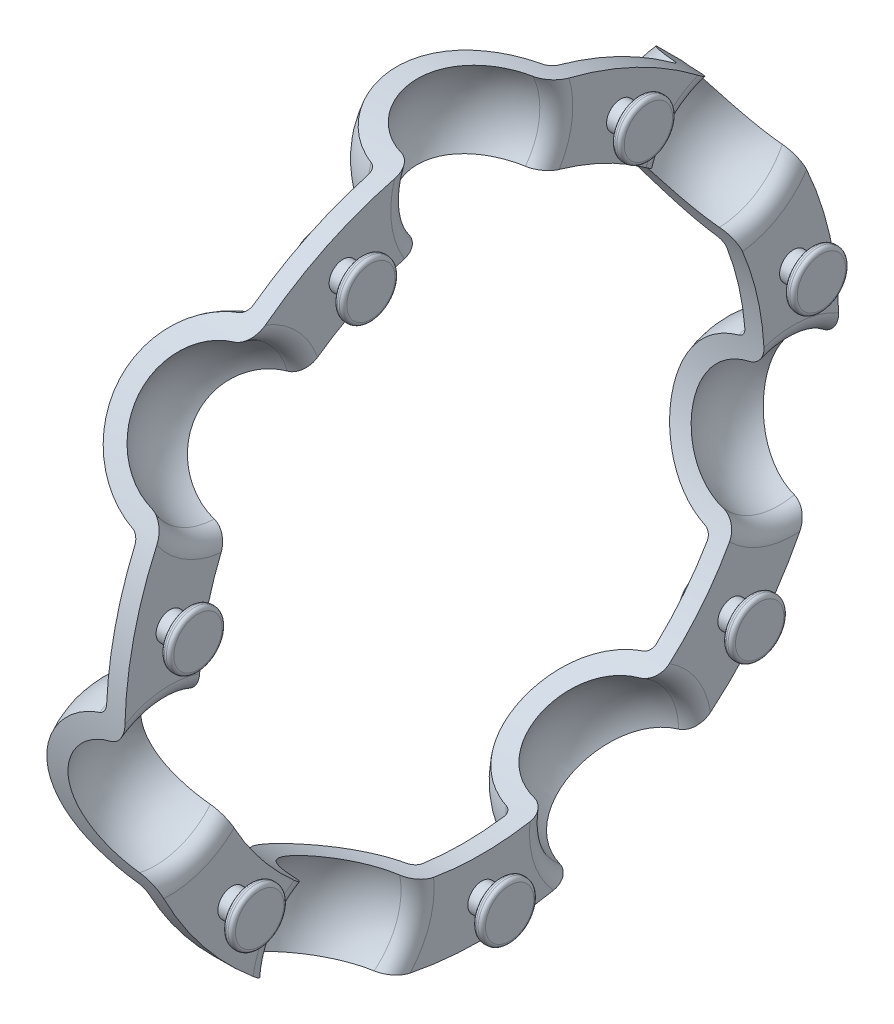
SolidWorks part; units mm, degrees
ref_plane "Front Plane" through (0, 0, 0) normal (0, 0, 1) x (1, 0, 0)
ref_plane "Top Plane" through (0, 0, 0) normal (0, 1, 0) x (1, 0, 0)
ref_plane "Right Plane" through (0, 0, 0) normal (1, 0, 0) x (0, 0, -1)
sketch "Sketch1" plane through (0, 0, 0) normal (1, 0, 0) x (0, 0, -1)
  circle A0 centre (0, 0) radius 23
  dimension "D1" = 46
extrude "Boss-Extrude1" add sketch "Sketch1" along normal blind 1
sketch "Sketch2" plane through (1, 0, 0) normal (1, 0, 0) x (0, 0, -1)
  line L0 (0, 0) -> (0, 17.2) construction
  line L1 (-5, 17.2) -> (5, 17.2)
  arc A0 (-5, 17.2) -> (5, 17.2) centre (0, 17.2) ccw
  point P5 (0, 17.2)
  dimension "D1" = 5
  dimension "D2" = 17.2
revolve "Revolve1" add sketch "Sketch2" angle 180 about L1
sketch "Sketch3" plane through (1, 0, 0) normal (1, 0, 0) x (0, 0, -1)
  line L0 (-4, 17.2) -> (4, 17.2)
  line L1 (0, 17.2) -> (0, 0) construction
  arc A0 (-4, 17.2) -> (4, 17.2) centre (0, 17.2) ccw
  dimension "D1" = 4
  dimension "D2" = 17.2
revolve "Cut-Revolve1" cut sketch "Sketch3" angle 180 about L0
fillet "Fillet1" radius 1 1 edges at (1, 17.2, -4)
fillet "Fillet2" radius 0.5 1 edges at (0, 17.2, -4.899)
pattern_circular "CirPattern1" count 7 over 360 about axis through (1, 0, 0) along (1, 0, 0) of "Revolve1", "Cut-Revolve1", "Fillet2", "Fillet1"
sketch "Sketch4" plane through (1, 0, 0) normal (1, 0, 0) x (0, 0, -1)
  circle A0 centre (0, 0) radius 15.2 construction
  circle A2 centre (0, 0) radius 19.2
  circle A3 centre (0, 0) radius 17.2 construction
  circle A5 centre (0, 0) radius 23
  circle A6 centre (0, 0) radius 23 construction
  dimension "D1" = 34.4
  dimension "D2" = 2
  dimension "D3" = 2
extrude "Cut-Extrude1" cut sketch "Sketch4" against normal through all
sketch "Sketch5" plane through (1, 0, 0) normal (1, 0, 0) x (0, 0, -1)
  circle A0 centre (0, 0) radius 15.2
  arc A1 (-4.6891, 18.6186) -> (-11.633, 15.2746) centre (0, 0) ccw construction
  dimension "D1" = 4
extrude "Cut-Extrude2" cut sketch "Sketch5" against normal through all
sketch "Sketch6" plane through (1, 0, 0) normal (1, 0, 0) x (0, 0, -1)
  line L1 (0, 0) -> (0, -17.2) construction
  circle A0 centre (0, 0) radius 17.2 construction
  circle A1 centre (0, -17.2) radius 0.75
  dimension "D1" = 34.4
  dimension "D2" = 1.5
extrude "Cut-Extrude3" cut sketch "Sketch6" against normal blind 1.5
pattern_circular "CirPattern2" count 7 over 360 about axis through (1, 0, 0) along (1, 0, 0) of "Cut-Extrude3"
sketch "Sketch9" plane through (1, 0, 0) normal (1, 0, 0) x (0, 0, -1)
  point P0 (0, -17.2)
sketch "Sketch10" plane through (0, 0, 0) normal (0, 0, 1) x (1, 0, 0)
  line L0 (1, -17.2) -> (2.5, -17.2) construction
  line L1 (2.5, -17.2) -> (2.5, -16.45)
  line L2 (1.9977, -16.45) -> (0, -16.45)
  line L3 (0, -16.45) -> (0, -15.9)
  line L4 (-0.2, -15.7) -> (-0.3, -15.7)
  line L5 (-0.5, -15.9) -> (-0.5, -17.2)
  line L6 (-0.5, -17.2) -> (2.5, -17.2)
  line L7 (1, -18.8093) -> (1, -14.9775) construction
  line L8 (1.9977, -16.45) -> (1.9977, -15.9)
  line L9 (2.1977, -15.7) -> (2.3, -15.7)
  line L10 (2.5, -15.9) -> (2.5, -16.45)
  line L11 (2.5, -16.45) -> (1.9977, -16.45) construction
  arc A0 (0, -15.9) -> (-0.2, -15.7) centre (-0.2, -15.9) ccw
  arc A1 (-0.3, -15.7) -> (-0.5, -15.9) centre (-0.3, -15.9) ccw
  arc A2 (2.3, -15.7) -> (2.5, -15.9) centre (2.3, -15.9) cw
  arc A3 (1.9977, -15.9) -> (2.1977, -15.7) centre (2.1977, -15.9) cw
  point P10 (0, -15.7)
  point P13 (-0.5, -15.7)
  point P21 (2.5, -15.7)
  dimension "D6" = 0.2
  dimension "D9" = 0.2
  dimension "D1" = 1.5
  dimension "D2" = 1
  dimension "D3" = 0.75
  dimension "D4" = 0.5
  dimension "D5" = 0.75
  dimension "D7" = 0.9977
  dimension "D8" = 0.75
revolve "Revolve2" add sketch "Sketch10" angle 360 about L0
pattern_circular "CirPattern5" count 7 over 360 about axis through (1, 0, 0) along (1, 0, 0) of bodies 109
